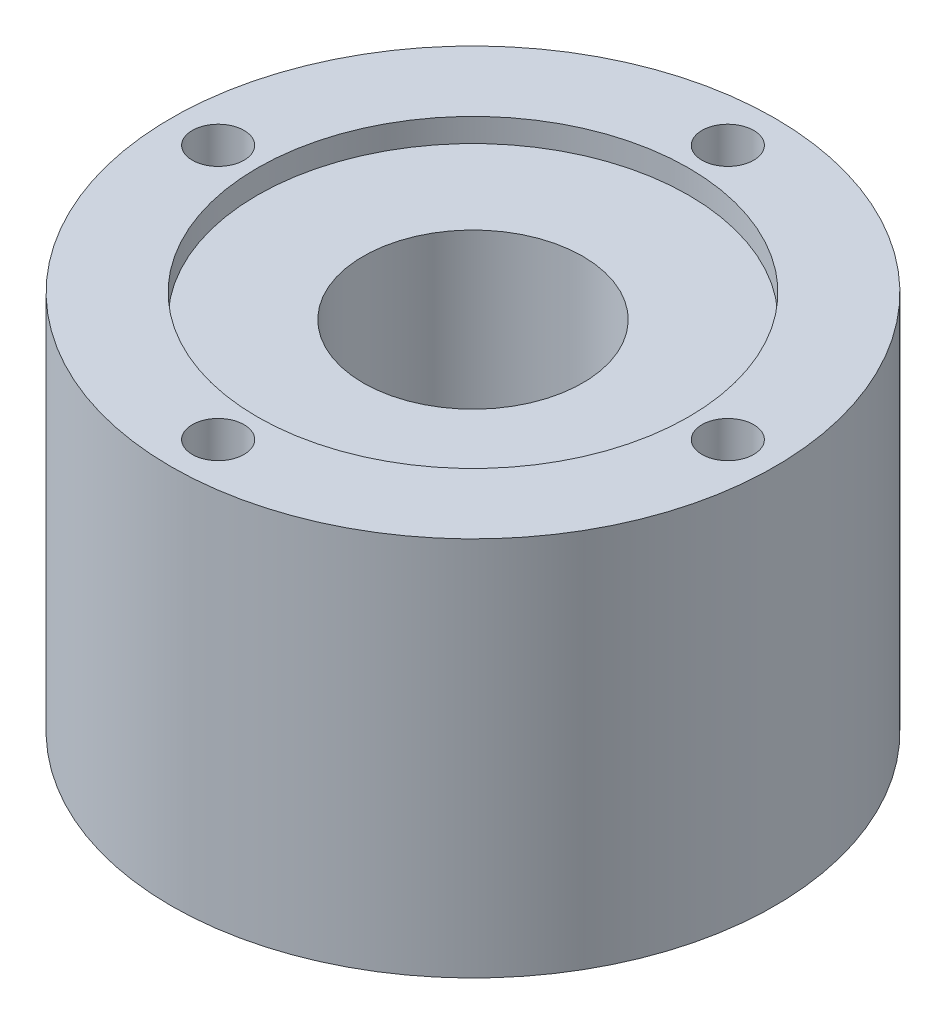
SolidWorks part; units mm, degrees
material "PA38 (3.3206)"
ref_plane "Płaszczyzna przednia" through (0, 0, 0) normal (0, 0, 1) x (1, 0, 0)
ref_plane "Płaszczyzna górna" through (0, 0, 0) normal (0, 1, 0) x (1, 0, 0)
ref_plane "Płaszczyzna prawa" through (0, 0, 0) normal (1, 0, 0) x (0, 0, -1)
sketch "Szkic1" plane through (0, 0, 0) normal (1, 0, 0) x (0, 0, -1)
  line L0 (0, 14) -> (0, -14) construction
  line L1 (-18.5, -14) -> (-38.5, -14)
  line L2 (-38.5, -14) -> (-38.5, 34.5)
  line L3 (-18.5, -14) -> (-18.5, 0)
  line L4 (-18.5, 0) -> (-14, 0)
  line L5 (-14, 0) -> (-14, 34.5)
  line L6 (-14, 34.5) -> (-38.5, 34.5)
  dimension "D1" = 37
  dimension "D2" = 28
  dimension "D3" = 14
  dimension "D4" = 77
  dimension "D5" = 48.5
revolve "Obrót1" add sketch "Szkic1" angle 360 about L0
hole_wizard "Otwór pod śrubę M61" positions "Szkic2" profile "Szkic3" hole size "M6" standard "DIN" end condition up to next
sketch "Szkic2" plane through (0, 34.5, 0) normal (0, 1, 0) x (1, 0, 0)
  line L0 (0, 0) -> (0, 32.5) construction
  point P0 (0, 32.5)
  dimension "D1" = 32.5
sketch "Szkic3" plane through (0, 34.5, -32.5) normal (1, 0, 0) x (0, 0, 1)
  line L0 (0, 0) -> (0, 48.501)
  line L1 (0, 48.501) -> (3.3, 48.501)
  line L2 (3.3, 48.501) -> (3.3, 0)
  line L5 (3.3, 0) -> (0, 0)
  line L11 (0, -6.35) -> (0, 107.95) construction
  dimension "Średnica otworu na wylot" = 6.6
  dimension "Głębokość otworu na wylot" = 48.501
pattern_circular "Szyk kołowy1" count 4 over 360 about axis through (0, 14, 0) along (0, 1, 0) of "Otwór pod śrubę M61" reverse direction yes
sketch "Szkic4" plane through (0, 34.5, 0) normal (0, 1, 0) x (1, 0, 0)
  circle A0 centre (0, 0) radius 27.5
  dimension "D1" = 55
extrude "Wytnij-wyciągnięcie1" cut sketch "Szkic4" against normal blind 3
